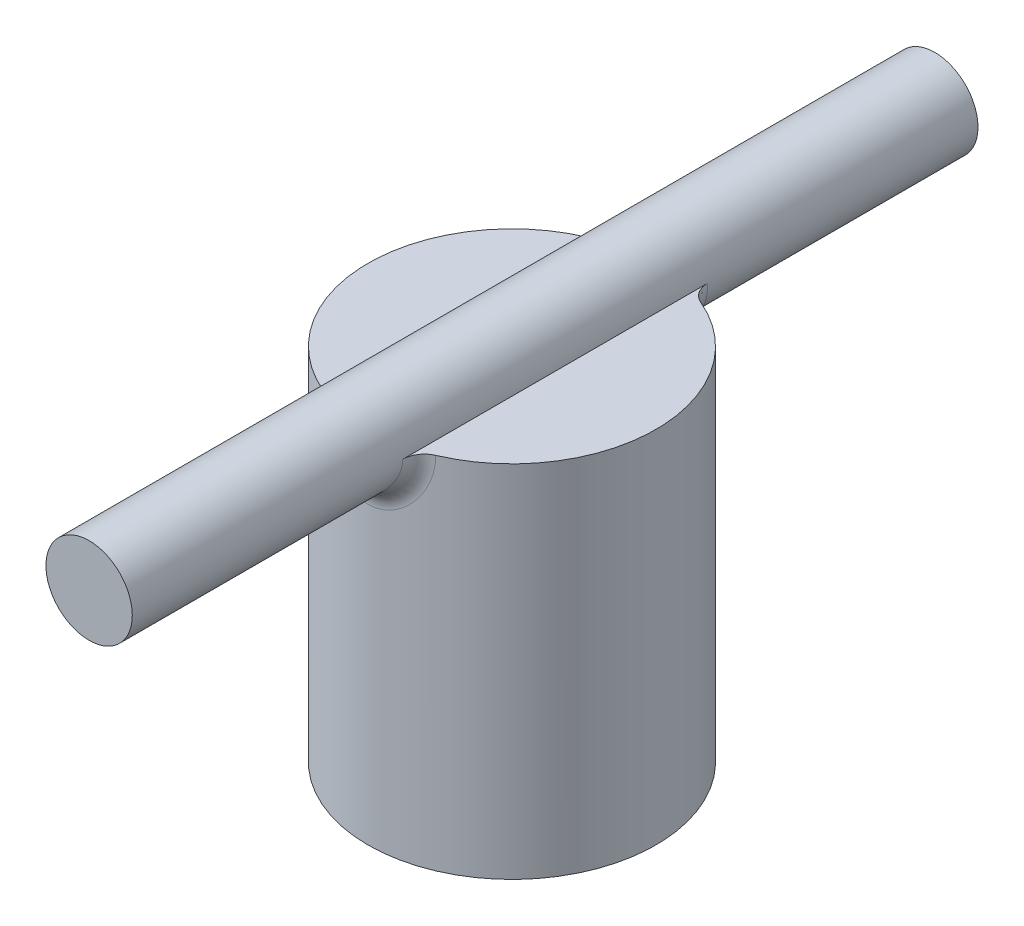
SolidWorks part; units mm, degrees
ref_plane "Front Plane" through (0, 0, 0) normal (0, 0, 1) x (1, 0, 0)
ref_plane "Top Plane" through (0, 0, 0) normal (0, 1, 0) x (1, 0, 0)
ref_plane "Right Plane" through (0, 0, 0) normal (1, 0, 0) x (0, 0, -1)
sketch "Sketch1" plane through (0, 0, 0) normal (0, 1, 0) x (1, 0, 0)
  circle A0 centre (0, 0) radius 20
  dimension "D1" = 40
extrude "Boss-Extrude1" add sketch "Sketch1" along normal blind 50 contours A0
sketch "Sketch2" plane through (0, 0, 0) normal (0, 0, 1) x (1, 0, 0)
  line L0 (20, 50) -> (-20, 50) construction
  circle A0 centre (0, 50) radius 6
  dimension "D1" = 12
extrude "Boss-Extrude2" add sketch "Sketch2" along normal mid plane 117.49
fillet "Fillet1" radius 3 2 edges at (0.891, 44.0665, -19.9801) (-1.4259, 44.1719, 19.9491)
ref_plane "Plane1" through (0, 30, 0) normal (0, 1, 0) x (1, 0, 0)
